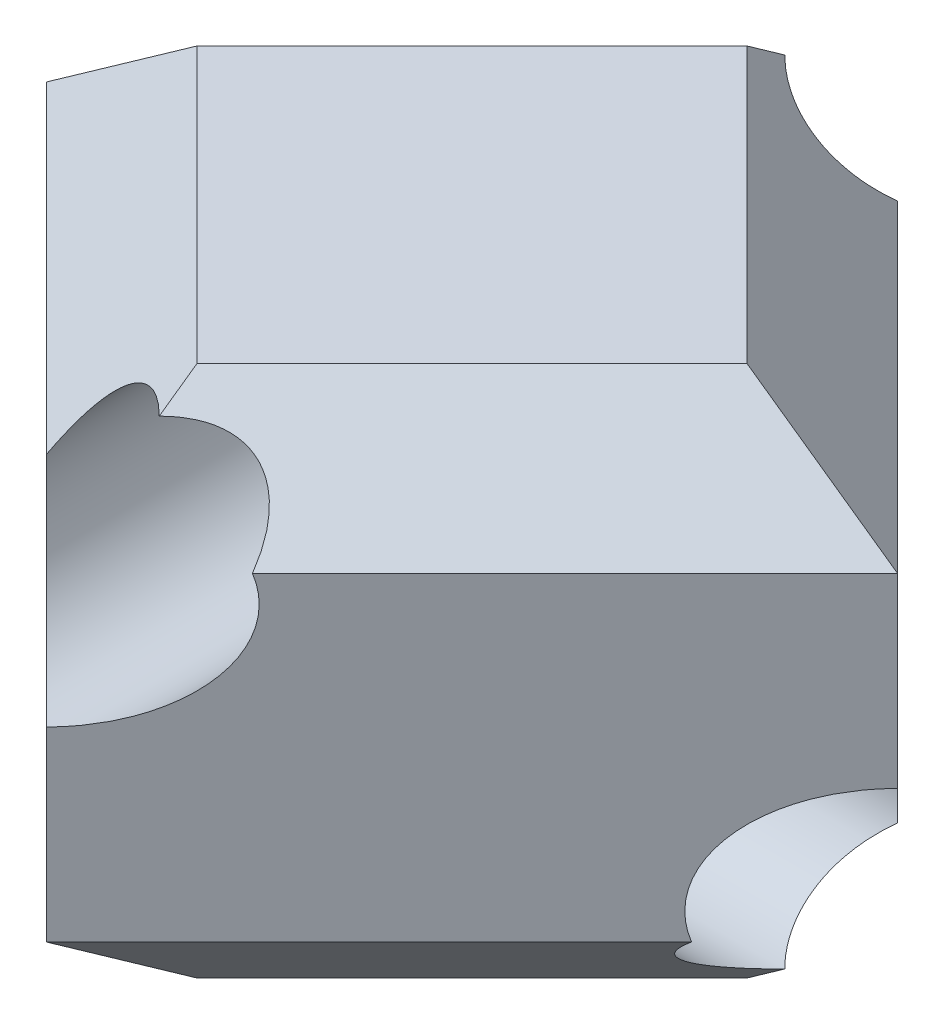
SolidWorks part; units mm, degrees
ref_plane "前基準面" through (0, 0, 0) normal (0, 0, 1) x (1, 0, 0)
ref_plane "上基準面" through (0, 0, 0) normal (0, 1, 0) x (1, 0, 0)
ref_plane "右基準面" through (0, 0, 0) normal (1, 0, 0) x (0, 0, -1)
sketch "草圖1" plane through (0, 0, 0) normal (0, 1, 0) x (1, 0, 0)
  line L0 (0, 0) -> (20, 20)
  line L1 (0, 0) -> (20, -20)
  line L2 (20, 20) -> (40, 0)
  line L3 (20, -20) -> (40, 0)
  line L4 (20, 20) -> (20, -20) construction
  line L5 (0, 0) -> (40, 0) construction
  dimension "D1" = 40
extrude "填料-伸長1" add sketch "草圖1" along normal blind 25
sketch "草圖2" plane through (0, 0, 0) normal (1, 0, 0) x (0, 0, -1)
  line L0 (0, 25) -> (0, 0) construction
  line L4 (0, 12.5) -> (0, 0) construction
  circle A0 centre (0, 6.25) radius 5
  point P4 (0, 13.5504)
  point P5 (0, 12.5)
  dimension "D1" = 10
extrude "除料-伸長2" cut sketch "草圖2" against normal through all and the other way through all
sketch "草圖3" plane through (0, 0, 0) normal (0, 0, 1) x (1, 0, 0)
  line L0 (20, 12.5) -> (20, 25) construction
  line L1 (20, 25) -> (20, 0) construction
  circle A0 centre (20, 18.75) radius 5
  dimension "D1" = 10
extrude "除料-伸長3" cut sketch "草圖3" against normal through all both and the other way through all
chamfer "導角1" distance 5 angle 45 8 edges at (30, 0, 10) (30, 0, -10) (10, 0, -10) (10, 0, 10) (10, 25, 10) (10, 25, -10) (30, 25, -10) (30, 25, 10)
